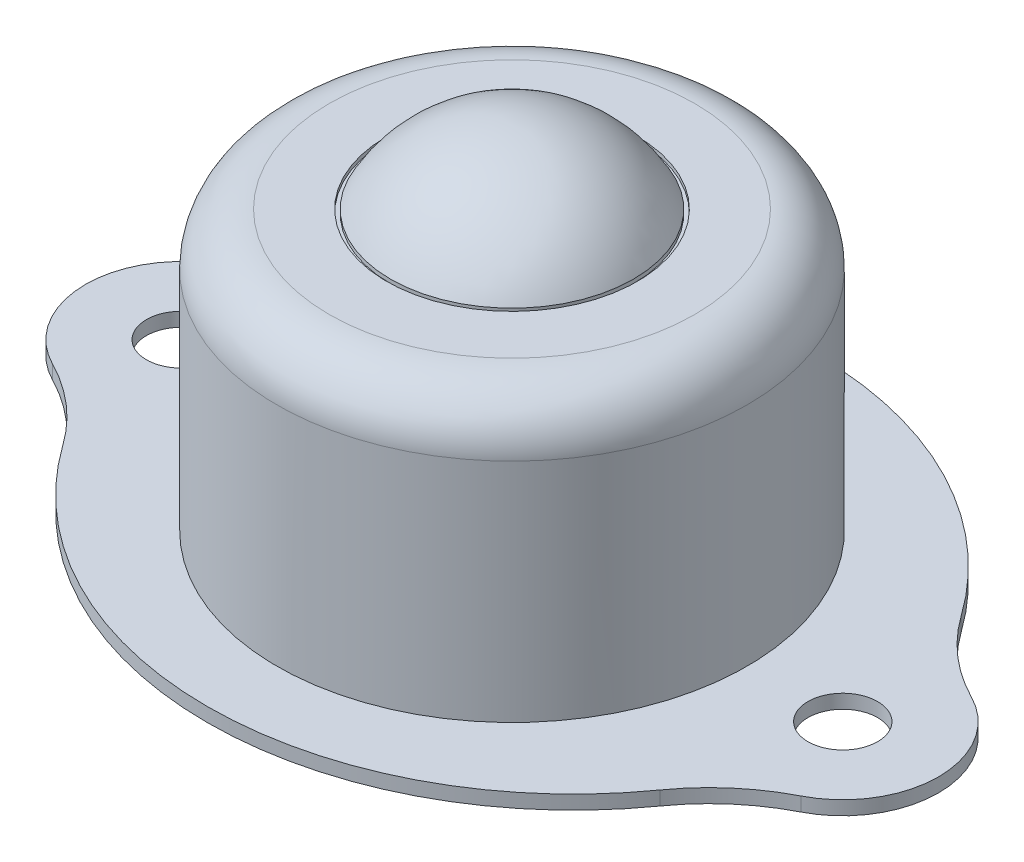
SolidWorks part; units mm, degrees
ref_plane "前视基准面" through (0, 0, 0) normal (0, 0, 1) x (1, 0, 0)
ref_plane "上视基准面" through (0, 0, 0) normal (0, 1, 0) x (1, 0, 0)
ref_plane "右视基准面" through (0, 0, 0) normal (1, 0, 0) x (0, 0, -1)
sketch "草图1" plane through (0, 0, 0) normal (0, 0, 1) x (1, 0, 0)
  line L0 (-6.98, 16.4) -> (13.5, 16.4)
  line L1 (0, 20.6) -> (0, -0.4)
  line L2 (-24.5, 0.4) -> (-13.5, 0.4)
  line L3 (-24.5, 0.4) -> (-24.5, -0.4)
  line L4 (-24.5, -0.4) -> (24.5, -0.4)
  line L5 (24.5, 0.4) -> (24.5, -0.4)
  line L7 (-7.2056, 16.4) -> (-7.2056, 16.1777)
  line L8 (-13.5, 16.4) -> (-7.2056, 16.4)
  line L9 (-13.5, 16.4) -> (-13.5, 0.4)
  line L11 (13.5, 16.4) -> (13.5, 0.4)
  line L17 (13.5, 0.4) -> (24.5, 0.4)
  line L18 (-7.2056, 16.1777) -> (-6.98, 16.1777)
  line L19 (-6.98, 16.4) -> (-6.98, 16.1777)
  arc A3 (6.98, 16.4) -> (-6.98, 16.4) centre (0, 12.7) ccw
  point P3 (0, 0)
  point P8 (0, 8.4)
  dimension "D1" = 49
  dimension "D2" = 0.8
  dimension "D3" = 27
  dimension "D5" = 16
  dimension "D7" = 13.1
revolve "旋转1" add sketch "草图1" angle 360 about L1 region at (-7.2076, 7.6994, 0)
revolve "旋转2" add sketch "草图1<3>" angle 360 about L1 region at (-2.7439, 18.1253, 0)
sketch "草图1<3>" plane through (0, 0, 0) normal (0, 0, 1) x (1, 0, 0) same geometry as "草图1"
fillet "圆角1" radius 3 1 edges at (-13.5, 16.4, 0)
sketch "草图2" plane through (0, -0.4, 0) normal (0, -1, 0) x (1, 0, 0)
  line L0 (-24.5, 0) -> (-13.5, 0) construction
  line L1 (13.5, 0) -> (24.5, 0) construction
  line L2 (-24.5, 0) -> (-17, 0) construction
  line L3 (17, 0) -> (24.5, 0) construction
  circle A0 centre (-19, 0) radius 2
  circle A1 centre (19, 0) radius 2
  circle A2 centre (0, 0) radius 24.5
  arc A3 (-21.4937, 4.9022) -> (-21.4937, -4.9022) centre (-19, 0) ccw
  arc A4 (21.4937, -4.9022) -> (21.4937, 4.9022) centre (19, 0) ccw
  arc A5 (-17.152, 8.6479) -> (17.152, 8.6479) centre (0, -3.5378) cw
  arc A6 (-17.152, -8.6479) -> (17.152, -8.6479) centre (0, 3.5378) ccw
  arc A7 (-17.152, -8.6479) -> (-21.4937, -4.9022) centre (-26.9345, -15.5979) ccw
  arc A8 (17.152, -8.6479) -> (21.4937, -4.9022) centre (26.9345, -15.5979) cw
  arc A9 (21.4937, 4.9022) -> (17.152, 8.6479) centre (26.9345, 15.5979) cw
  arc A10 (-17.152, 8.6479) -> (-21.4937, 4.9022) centre (-26.9345, 15.5979) cw
  point P23 (-19, -5.5)
  point P26 (19, -5.5)
  point P29 (19, 5.5)
  point P32 (-19, 5.5)
  circle M2 centre (0, 0) radius 24.5
  dimension "D1" = 38
  dimension "D3" = 4
  dimension "D4" = 4
  dimension "D5" = 12
  dimension "D2" = 19
extrude "切除-拉伸1" cut sketch "草图2" against normal blind 10 contours A10 A5 A9 A4 A2 A3 | A8 A6 A7 A3 A4 M2 | A0 | A1 region at (-19, -0.4, 0) region at (19, -0.4, 0) region at (24.1556, -0.4, 3.1617) region at (0, -0.4, -23.9522)
